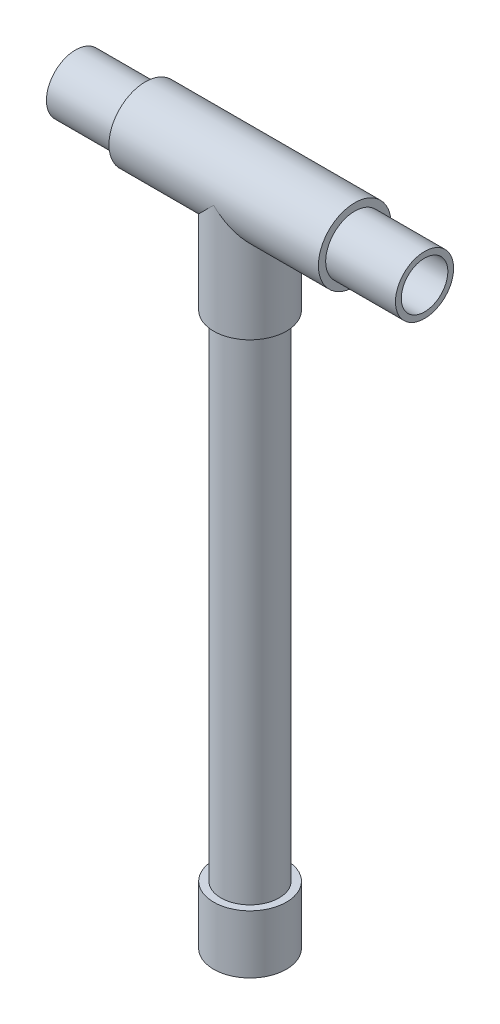
SolidWorks part; units mm, degrees
ref_plane "前视基准面" through (0, 0, 0) normal (0, 0, 1) x (1, 0, 0)
ref_plane "上视基准面" through (0, 0, 0) normal (0, 1, 0) x (1, 0, 0)
ref_plane "右视基准面" through (0, 0, 0) normal (1, 0, 0) x (0, 0, -1)
sketch "草图1" plane through (0, 0, 0) normal (0, 0, 1) x (1, 0, 0)
  line L0 (-1459.5572, 0) -> (71518.3052, 0) construction
  line L1 (0, -1459.5572) -> (0, 71518.3052) construction
  line L2 (0, 0) -> (-12.5, 0) construction
  line L3 (-12.5, 0) -> (-12.5, -37.5)
  line L4 (-12.5, -37.5) -> (-10, -37.5)
  line L5 (-10, -37.5) -> (-10, -207.5)
  line L6 (-10, -207.5) -> (-12.5, -207.5)
  line L7 (-12.5, -207.5) -> (-12.5, -227.5)
  line L8 (-12.5, -227.5) -> (0, -227.5)
  line L9 (0, -227.5) -> (0, 0) construction
  line L10 (-8, 0) -> (-8, -207.5916)
  line L11 (-8, -207.5916) -> (0, -207.5916)
  line L12 (0, -207.5916) -> (0, -227.5)
  line L13 (-12.5, 0) -> (-8, 0)
  dimension "D1" = 20
  dimension "D2" = 37.5
  dimension "D3" = 227.5
  dimension "D4" = 20
  dimension "D5" = 25
  dimension "D6" = 16
revolve "丨" add sketch "草图1" angle 360 about L1
sketch "草图3" plane through (0, 0, 0) normal (0, 1, 0) x (1, 0, 0)
  line L0 (-1000, 0) -> (49000, 0) construction
  line L1 (0, -1000) -> (0, 49000) construction
  line L3 (-60, 10) -> (-40, 10)
  line L9 (60, 0) -> (60.3645, 0) construction
  line L10 (-40, 10) -> (-36, 10)
  line L11 (-36, 10) -> (-36, 12.5)
  line L12 (-36, 12.5) -> (36, 12.5)
  line L13 (36, 12.5) -> (36, 10)
  line L14 (36, 10) -> (60, 10)
  line L17 (-60, 8) -> (60, 8)
  line L20 (-60, 10) -> (-60, 8)
  line L21 (60, 10) -> (60, 8)
  point P9 (59.6673, 8)
  point P11 (0, 0)
  point P15 (0, 0)
  point P19 (0, 0)
  point P20 (0, 0)
  point P21 (60.3645, 0)
  dimension "D1" = 72
  dimension "D2" = 12.5
  dimension "D3" = 120
  dimension "D4" = 20
  dimension "D5" = 10
  dimension "D6" = 16
  dimension "D7" = 4
revolve "一" add sketch "草图3" angle 360 about L9
